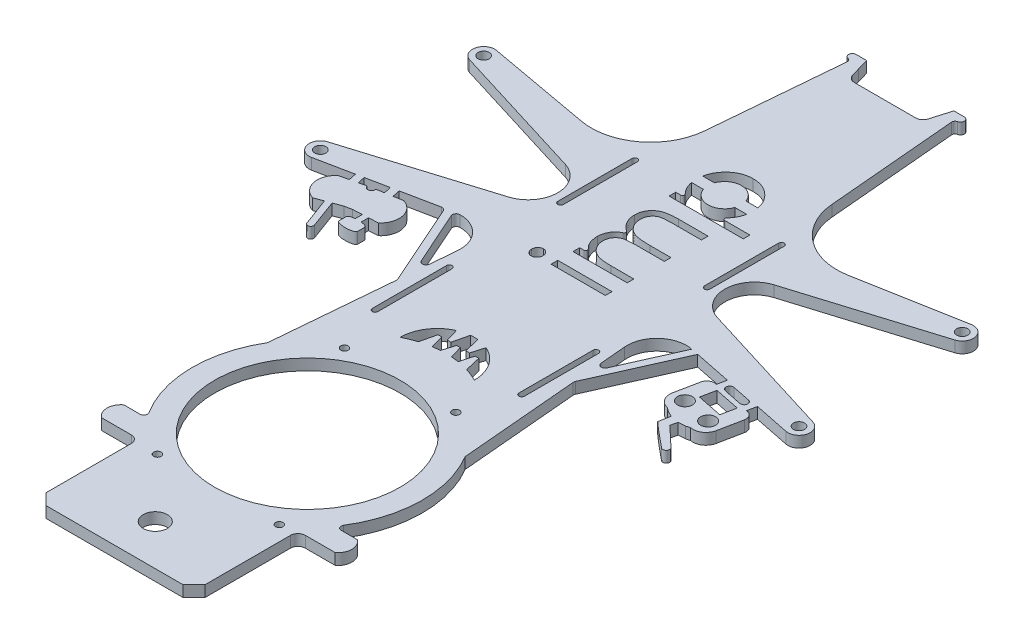
SolidWorks part; units mm, degrees
ref_plane "前视基准面" through (0, 0, 0) normal (0, 0, 1) x (1, 0, 0)
ref_plane "上视基准面" through (0, 0, 0) normal (0, 1, 0) x (1, 0, 0)
ref_plane "右视基准面" through (0, 0, 0) normal (1, 0, 0) x (0, 0, -1)
sketch "草图1" plane through (0, 0, 0) normal (0, 1, 0) x (1, 0, 0)
  line L5 (-65.3843, -19.1333) -> (-28.1418, -7.6445)
  line L6 (-63.9021, -24.9398) -> (-56.5526, -23.4451)
  line L8 (0, 0) -> (0, 91.5573) construction
  line L9 (0, 0) -> (-115.8836, 0) construction
  line L15 (0, 0) -> (0, -124.2991) construction
  line L16 (-15, -65) -> (15, -65) construction
  line L20 (-15.42, -115) -> (17.43, -115) construction
  line L21 (-28, -109.5) -> (-28, -90)
  line L22 (28, -109.5) -> (28, -90)
  line L23 (-17.5, -120) -> (17.5, -120)
  line L28 (22.5, -27) -> (22.5, 27) construction
  line L29 (-22.5, -27) -> (-22.5, 27) construction
  line L30 (28.1418, -7.6445) -> (65.3843, -19.1333)
  line L31 (28.1418, 7.6445) -> (65.3843, 19.1333)
  line L32 (-28, -90) -> (28, -90) construction
  line L33 (28, -90) -> (22.5, -27)
  line L34 (-28, -90) -> (-22.5, -27)
  line L36 (0, 0) -> (104.501, 0) construction
  line L37 (-28.1418, 7.6445) -> (-65.3843, 19.1333)
  line L39 (22.5, 70) -> (22.5, 27) construction
  line L40 (-22.5, 70) -> (-22.5, 27) construction
  line L41 (31.9307, 19.129) -> (63.9635, 24.9516) construction
  line L42 (-63.9635, 24.9516) -> (-31.9307, 19.129) construction
  line L43 (-17.1562, 34.2114) -> (-14.0779, 69.4717)
  line L44 (63.9635, 24.9516) -> (35.957, 19.8608)
  line L45 (-63.9635, 24.9516) -> (-35.957, 19.8608)
  line L46 (17.1562, 34.2114) -> (14.0779, 69.4717)
  line L51 (-49.203, -21.9504) -> (-47.2101, -31.7498) construction
  line L58 (-48.19, -31.9491) -> (-46.2301, -31.5505)
  line L59 (-41.8535, -20.4557) -> (-32.0641, -18.4647)
  line L65 (-14.4088, 65.6811) -> (14.4088, 65.6811) construction
  line L70 (-10.8845, 69.4717) -> (-10.1819, 67.1107)
  line L75 (10.8788, 69.4717) -> (10.1832, 67.115)
  line L76 (-8.265, 65.6811) -> (8.265, 65.6811)
  line L77 (-56.5526, -23.4451) -> (-41.8535, -20.4557) construction
  line L78 (-46.2301, -31.5505) -> (-43.7558, -31.4316)
  line L79 (-48.19, -31.9491) -> (-50.5246, -32.81)
  line L80 (-54.3603, -34.2244) -> (-39.6612, -31.235) construction
  line L81 (-48.7048, -24.4002) -> (-49.7844, -24.1095) construction
  line L82 (-48.7048, -24.4002) -> (-47.8245, -23.711) construction
  line L84 (41.8535, -20.4557) -> (32.0641, -18.4647)
  line L101 (-49.7844, -24.1095) -> (-47.8245, -23.711) construction
  line L103 (63.9021, -24.9398) -> (56.5526, -23.4451)
  line L106 (41.8535, -20.4557) -> (56.5526, -23.4451) construction
  line L107 (42.3935, -35.3623) -> (50.233, -36.9567) construction
  line L108 (39.6612, -31.235) -> (40.9566, -24.8654)
  line L109 (43.3151, -23.3041) -> (43.6091, -23.3639)
  line L110 (54.3603, -34.2244) -> (55.6557, -27.8548)
  line L111 (38.9637, -34.6648) -> (56.0543, -25.8949) construction
  line L112 (41.3552, -22.9055) -> (53.6628, -37.6542) construction
  line L113 (49.203, -21.9504) -> (41.4195, -60.2218) construction
  line L114 (43.6091, -23.3639) -> (44.8847, -23.1131) construction
  line L115 (44.8847, -23.1131) -> (52.7242, -24.7074) construction
  line L116 (52.7242, -24.7074) -> (53.8005, -25.4366) construction
  line L117 (53.8005, -25.4366) -> (54.0944, -25.4964)
  line L120 (44.938, -36.9003) -> (47.2899, -37.3786) construction
  line L121 (45.4995, -45.1782) -> (43.5396, -44.7797) construction
  line L122 (45.4995, -45.1782) -> (47.2899, -37.3786) construction
  line L123 (43.5396, -44.7797) -> (44.938, -36.9003) construction
  line L124 (43.2738, -36.0516) -> (49.1534, -37.2474) construction
  line L125 (47.2899, -37.3786) -> (49.1534, -37.2474)
  line L126 (44.938, -36.9003) -> (43.2738, -36.0516)
  line L127 (43.2738, -36.0516) -> (42.3935, -35.3623)
  line L128 (49.1534, -37.2474) -> (50.233, -36.9567)
  line L129 (43.1907, -31.4426) -> (51.0302, -33.0369) construction
  line L130 (40.7168, -24.8097) -> (55.8983, -27.8973) construction
  line L131 (52.7242, -24.7074) -> (53.1228, -22.7476) construction
  line L132 (44.8847, -23.1131) -> (45.2833, -21.1532) construction
  line L133 (53.1228, -22.7476) -> (56.5526, -23.4451) construction
  line L134 (41.8535, -20.4557) -> (45.2833, -21.1532) construction
  line L135 (45.6157, -39.5893) -> (53.5856, -46.6394) construction
  line L136 (44.3922, -39.9756) -> (46.3849, -41.7383)
  line L137 (46.8657, -39.2264) -> (47.8425, -40.0905)
  line L138 (47.8425, -40.0905) -> (46.3849, -41.7383) construction
  line L139 (47.2899, -37.3786) -> (46.8657, -39.2264)
  line L140 (44.938, -36.9003) -> (44.3922, -39.9756)
  line L141 (51.0114, -45.5639) -> (52.204, -44.2157) construction
  line L142 (47.8425, -40.0905) -> (52.204, -44.2157)
  line L143 (46.3849, -41.7383) -> (51.0114, -45.5639)
  line L144 (53.8005, -25.4366) -> (54.2987, -22.9867)
  line L145 (45.0757, -24.6826) -> (51.9353, -26.0777)
  line L146 (45.0757, -24.6826) -> (44.2785, -28.6024)
  line L147 (44.2785, -28.6024) -> (51.1381, -29.9975)
  line L148 (51.9353, -26.0777) -> (51.1381, -29.9975)
  line L149 (45.0757, -24.6826) -> (51.1381, -29.9975) construction
  line L150 (44.2785, -28.6024) -> (51.9353, -26.0777) construction
  line L151 (54.2987, -22.9867) -> (56.5526, -23.4451)
  line L152 (43.6091, -23.3639) -> (44.1073, -20.914)
  line L153 (41.8535, -20.4557) -> (44.1073, -20.914)
  line L154 (-47.8245, -23.711) -> (-45.8523, -23.3727)
  line L155 (-49.7844, -24.1095) -> (-51.732, -24.5684)
  line L156 (-56.1141, -25.601) -> (-48.1766, -23.9867) construction
  line L157 (-52.91, -29.4394) -> (-42.8653, -27.3966) construction
  line L158 (-42.9558, -31.3932) -> (-42.9558, -37.0074) construction
  line L159 (-51.2752, -33.0867) -> (-49.3498, -38.3078) construction
  line L160 (-49.3498, -38.3078) -> (-42.9558, -37.0074) construction
  line L161 (-41.8535, -20.4557) -> (-44.3033, -20.9539)
  line L162 (-44.3033, -20.9539) -> (-43.8802, -23.0344)
  line L163 (-45.8523, -23.3727) -> (-46.2632, -21.3525)
  line L164 (-56.5526, -23.4451) -> (-54.1027, -22.9469)
  line L165 (-54.1027, -22.9469) -> (-53.6796, -25.0273)
  line L166 (-51.732, -24.5684) -> (-52.1428, -22.5483)
  line L167 (-52.1428, -22.5483) -> (-46.2632, -21.3525)
  line L168 (-53.6796, -25.0273) -> (-56.1141, -25.601)
  line L169 (-43.8802, -23.0344) -> (-41.415, -22.6115)
  line L170 (-43.7558, -31.4316) -> (-43.7558, -33.3548)
  line L171 (-42.1558, -31.3548) -> (-42.1558, -33.3548)
  line L172 (-42.1558, -31.3548) -> (-39.6612, -31.235)
  line L173 (-45.4558, -34.0654) -> (-40.4558, -34.0654) construction
  line L174 (-42.9558, -34.8154) -> (-42.9558, -33.3154) construction
  line L175 (-45.4558, -36.0654) -> (-40.4558, -36.0654) construction
  line L176 (-42.9558, -36.8154) -> (-42.9558, -35.3154) construction
  line L177 (-40.4558, -36.0654) -> (-40.4558, -34.0654)
  line L178 (-45.4558, -36.0654) -> (-45.4558, -34.0654)
  line L179 (-50.5246, -32.81) -> (-47.7567, -40.3159)
  line L180 (-52.0257, -33.3635) -> (-49.2579, -40.8695)
  line L181 (-52.0257, -33.3635) -> (-54.3603, -34.2244)
  line L182 (11.7642, 72.4717) -> (14.5779, 72.4717)
  line L183 (-11.7642, 72.4717) -> (-14.5779, 72.4717)
  line L184 (11.7642, 72.4717) -> (10.8788, 69.4717)
  line L185 (-11.7642, 72.4717) -> (-10.8845, 69.4717)
  line L186 (46.5041, -22.6771) -> (51.4037, -23.6735) construction
  line L187 (46.7033, -21.6971) -> (51.603, -22.6936)
  line L188 (46.3048, -23.657) -> (51.2045, -24.6535)
  circle A0 centre (-64.5, 30) radius 1.5 construction
  circle A1 centre (64.5, 30) radius 1.5 construction
  circle A2 centre (64.5, -30) radius 1.5 construction
  circle A3 centre (-64.5, -30) radius 1.5 construction
  circle A4 centre (-64.5, 30) radius 3 construction
  circle A5 centre (64.5, 30) radius 3 construction
  circle A6 centre (64.5, -30) radius 3 construction
  circle A7 centre (-64.5, -30) radius 3 construction
  circle A10 centre (-64.5, 22) radius 1.5
  circle A11 centre (64.5, 22) radius 1.5
  circle A12 centre (64.5, -22) radius 1.5
  circle A13 centre (-64.5, -22) radius 1.5
  circle A22 centre (0, -90) radius 25
  circle A23 centre (-15, -65) radius 1
  circle A24 centre (15, -65) radius 1
  circle A25 centre (-15.42, -115) radius 1
  circle A26 centre (17.43, -115) radius 1
  arc A27 (-17.5, -120) -> (-28, -109.5) centre (-17.5, -109.5) cw
  arc A28 (17.5, -120) -> (28, -109.5) centre (17.5, -109.5) ccw
  arc A42 (63.9021, -24.9398) -> (65.3843, -19.1333) centre (64.5, -22) ccw
  arc A43 (65.3843, 19.1333) -> (63.9635, 24.9516) centre (64.5, 22) ccw
  arc A44 (28.1418, -7.6445) -> (28.1418, 7.6445) centre (30.5, 0) cw
  arc A47 (-65.3843, -19.1333) -> (-63.9021, -24.9398) centre (-64.5, -22) ccw
  arc A49 (-28.1418, -7.6445) -> (-28.1418, 7.6445) centre (-30.5, 0) ccw
  arc A50 (-22.5, -27) -> (-32.0641, -18.4647) centre (-30.4697, -26.3042) ccw
  arc A51 (-63.9635, 24.9516) -> (-65.3843, 19.1333) centre (-64.5, 22) ccw
  arc A52 (31.9307, 19.129) -> (22.5, 27) centre (30.5, 27) cw construction
  arc A53 (-31.9307, 19.129) -> (-22.5, 27) centre (-30.5, 27) ccw construction
  arc A54 (-35.957, 19.8608) -> (-17.1562, 34.2114) centre (-33.0955, 35.6029) ccw
  arc A55 (17.1562, 34.2114) -> (35.957, 19.8608) centre (33.0955, 35.6029) ccw
  arc A56 (-8.265, 65.6811) -> (-10.1819, 67.1107) centre (-8.265, 67.6811) cw
  arc A57 (10.1832, 67.115) -> (8.265, 65.6811) centre (8.265, 67.6811) cw
  arc A79 (22.5, -27) -> (32.0641, -18.4647) centre (30.4697, -26.3042) cw
  arc A80 (55.6557, -27.8548) -> (54.0944, -25.4964) centre (53.6959, -27.4562) ccw
  arc A81 (40.9566, -24.8654) -> (43.3151, -23.3041) centre (42.9165, -25.264) cw
  arc A83 (43.5396, -44.7797) -> (45.4995, -45.1782) centre (44.5196, -44.9789) ccw construction
  arc A84 (54.3603, -34.2244) -> (50.233, -36.9567) centre (50.9305, -33.5269) cw
  arc A85 (39.6612, -31.235) -> (42.3935, -35.3623) centre (43.091, -31.9325) ccw
  circle A86 centre (43.1907, -31.4426) radius 2
  circle A87 centre (51.0302, -33.0369) radius 2
  arc A88 (44.8847, -23.1131) -> (41.8535, -20.4557) centre (40.7168, -24.8097) ccw construction
  arc A89 (52.7242, -24.7074) -> (56.5526, -23.4451) centre (55.8983, -27.8973) cw construction
  arc A90 (51.0114, -45.5639) -> (52.204, -44.2157) centre (51.6077, -44.8898) ccw
  arc A91 (-39.6612, -31.235) -> (-41.415, -22.6115) centre (-42.8653, -27.3966) ccw
  arc A92 (-54.3603, -34.2244) -> (-56.1141, -25.601) centre (-52.91, -29.4394) cw
  arc A93 (-49.2579, -40.8695) -> (-47.7567, -40.3159) centre (-48.5073, -40.5927) ccw
  arc A94 (14.5779, 72.4717) -> (14.7779, 70.4717) centre (14.5779, 71.4617) cw
  arc A95 (14.0779, 69.4717) -> (14.7779, 70.4717) centre (14.9532, 69.604) cw
  arc A96 (-14.0779, 69.4717) -> (-14.7779, 70.4717) centre (-14.9532, 69.604) ccw
  arc A97 (-14.5779, 72.4717) -> (-14.7779, 70.4717) centre (-14.5779, 71.4617) ccw
  arc A98 (-49.7844, -24.1095) -> (-47.8245, -23.711) centre (-48.8044, -23.9103) ccw
  arc A99 (46.7033, -21.6971) -> (46.3048, -23.657) centre (46.5041, -22.6771) ccw
  arc A100 (51.2045, -24.6535) -> (51.603, -22.6936) centre (51.4037, -23.6735) ccw
  ellipse E0 centre (-42.9558, -36.0654) end of major axis (-40.4558, -36.0654) minor radius 0.75 (-45.4558, -36.0654) -> (-40.4558, -36.0654) ccw
  ellipse E1 centre (-42.9558, -34.0654) end of major axis (-45.4558, -34.0654) minor radius 0.75 (-40.4558, -34.0654) -> (-42.1558, -33.3548) ccw
  ellipse E2 centre (-42.9558, -34.0654) end of major axis (-45.4558, -34.0654) minor radius 0.75 (-43.7558, -33.3548) -> (-45.4558, -34.0654) ccw
  point P0 (0, 0)
  point P55 (47.509, -30.2799)
  point P109 (-9.7565, 65.6811)
  point P112 (9.76, 65.6811)
  point P182 (48.1069, -27.34)
  point P213 (48.9539, -23.1753)
  point P227 (0, 0)
  dimension "D1" = 3
  dimension "D6" = 6
  dimension "D7" = 6
  dimension "D8" = 6
  dimension "D9" = 6
  dimension "D15" = 3
  dimension "D18" = 6
  dimension "D19" = 16
  dimension "D20" = 8
  dimension "D21" = 22
  dimension "D22" = 50
  dimension "D28" = 2
  dimension "D31" = 2
  dimension "D25" = 45
  dimension "D37" = 27
  dimension "D38" = 16
  dimension "D39" = 15
  dimension "D40" = 12
  dimension "D41" = 6
  dimension "D44" = 8
  dimension "D45" = 5.2
  dimension "D27" = 22.5
  dimension "D47" = 10.5
  dimension "D48" = 15
  dimension "D17" = 8
  dimension "D12" = 6
  dimension "D13" = 8
  dimension "D16" = 8
  dimension "D60" = 2
  dimension "D61" = 2
  dimension "D62" = 1
  dimension "D67" = 7.5
  dimension "D70" = 0.2
  dimension "D74" = 6
  dimension "D77" = 0.8
  dimension "D81" = 2.4
  dimension "D66" = 2
  dimension "D86" = 1
  dimension "D90" = 3
  dimension "D93" = 2
  dimension "D79" = 2.4743
  dimension "D82" = 1
  dimension "D87" = 1
  dimension "D91" = 3.5
  dimension "D92" = 3.5
  dimension "D102" = 4
  dimension "D103" = 4.5
  dimension "D114" = 0.9
  dimension "D68" = 5
  dimension "D69" = 5
  dimension "D78" = 5
  dimension "D130" = 0.5
  dimension "D96" = 1
  dimension "D2" = 129
  dimension "D3" = 60
  dimension "D4" = 30
  dimension "D5" = 64.5
  dimension "D11" = 27
  dimension "D14" = 9.7565
  dimension "D23" = 30
  dimension "D24" = 15
  dimension "D26" = 30
  dimension "D29" = 32.85
  dimension "D30" = 2.43
  dimension "D32" = 27
  dimension "D33" = 28
  dimension "D34" = 28
  dimension "D35" = 35
  dimension "D36" = 17.5
  dimension "D42" = 45
  dimension "D43" = 5.2
  dimension "D46" = 120
  dimension "D49" = 2.4933
  dimension "D50" = 2
  dimension "D51" = 1
  dimension "D52" = 15
  dimension "D53" = 7.5
  dimension "D54" = 0.5
  dimension "D55" = 4
  dimension "D56" = 4
  dimension "D57" = 65.6811
  dimension "D58" = 10.1819
  dimension "D59" = 10.1832
  dimension "D63" = 2
  dimension "D64" = 0.8
  dimension "D65" = 15
  dimension "D71" = 8
  dimension "D72" = 2
  dimension "D73" = 2.5
  dimension "D75" = 5
  dimension "D76" = 2
  dimension "D80" = 2
  dimension "D83" = 8
  dimension "D84" = 1.2
  dimension "D85" = 1
  dimension "D88" = 0.5
  dimension "D89" = 3
  dimension "D94" = 4
  dimension "D95" = 4
  dimension "D97" = 8.265
  dimension "D98" = 3.7906
  dimension "D99" = 8.265
  dimension "D100" = 9.76
  dimension "D101" = 22.5
  dimension "D104" = 60
  dimension "D105" = 10.8845
  dimension "D106" = 10.8788
  dimension "D107" = 2.5
  dimension "D108" = 1.1
  dimension "D109" = 1.1
  dimension "D110" = 2
  dimension "D111" = 0.9
  dimension "D112" = 0.9
  dimension "D113" = 6
  dimension "D115" = 4
  dimension "D116" = 7
  dimension "D117" = 1.5
  dimension "D118" = 5
  dimension "D119" = 1.5
  dimension "D120" = 1.5
  dimension "D121" = 2
  dimension "D122" = 2
  dimension "D123" = 1.6
  dimension "D124" = 0.8
  dimension "D125" = 8
  dimension "D126" = 2.4882
  dimension "D127" = 3
  dimension "D128" = 0.2
  dimension "D129" = 1
  dimension "D131" = 1.25
  dimension "D132" = 2
  dimension "D133" = 5
extrude "凸台-拉伸1" add sketch "草图1" along normal blind 3
sketch "草图2" plane through (0, 0, 0) normal (0, -1, 0) x (1, 0, 0)
  line L0 (0, 133.3282) -> (0, -97.043) construction
  line L1 (-19.75, 2) -> (-19.75, -18) construction
  line L2 (-19, 2) -> (-19, -18)
  line L3 (-20.5, 2) -> (-20.5, -18)
  line L4 (19.75, 2) -> (19.75, -18) construction
  line L5 (20.5, 2) -> (20.5, -18)
  line L6 (19, 2) -> (19, -18)
  line L7 (0, 0) -> (56.7659, 0) construction
  line L8 (-19.75, 52) -> (-19.75, 32) construction
  line L9 (-19, 52) -> (-19, 32)
  line L10 (-20.5, 52) -> (-20.5, 32)
  line L11 (19.75, 52) -> (19.75, 32) construction
  line L12 (20.5, 52) -> (20.5, 32)
  line L13 (19, 52) -> (19, 32)
  arc A0 (-19, 2) -> (-20.5, 2) centre (-19.75, 2) ccw
  arc A1 (-20.5, -18) -> (-19, -18) centre (-19.75, -18) ccw
  arc A2 (20.5, 2) -> (19, 2) centre (19.75, 2) ccw
  arc A3 (19, -18) -> (20.5, -18) centre (19.75, -18) ccw
  arc A4 (-19, 52) -> (-20.5, 52) centre (-19.75, 52) ccw
  arc A5 (-20.5, 32) -> (-19, 32) centre (-19.75, 32) ccw
  arc A6 (20.5, 52) -> (19, 52) centre (19.75, 52) ccw
  arc A7 (19, 32) -> (20.5, 32) centre (19.75, 32) ccw
  arc A8 (-10, 55) -> (10, 55) centre (0, 55) ccw
  arc A9 (-10, 55) -> (10, 55) centre (0, 74.5959) ccw
  point P5 (-19.75, -8)
  point P10 (19.75, -8)
  point P19 (-19.75, 42)
  point P26 (19.75, 42)
  dimension "D6" = 42
  dimension "D8" = 10
  dimension "D9" = 22
  dimension "D1" = 1.5
  dimension "D2" = 20
  dimension "D3" = 19
  dimension "D4" = 19
  dimension "D5" = 8
  dimension "D7" = 55
  dimension "D10" = 10
extrude "切除-拉伸1" cut sketch "草图2" against normal blind 3
sketch "草图3" plane through (0, 0, 0) normal (0, -1, 0) x (1, 0, 0)
  line L0 (0, 67.5428) -> (0, 45) construction
  line L1 (-5, 60.2388) -> (-5, 45) construction
  line L2 (5, 60.0167) -> (5, 45) construction
  line L3 (-1.5, 52.6471) -> (-0.5, 49.2959)
  line L4 (0.5, 49.2959) -> (1.5, 52.6471)
  line L5 (-5, 48.7959) -> (5, 48.7959) construction
  line L6 (-4.5, 49.2959) -> (-3.5, 52.8761)
  line L7 (-6.5, 53.5781) -> (-5.5, 49.2959)
  line L8 (4.5, 49.2959) -> (3.5, 52.8761)
  line L9 (5.5, 49.2959) -> (6.5, 53.5781)
  line L10 (-5, 52.5959) -> (5, 52.5959) construction
  line L11 (-5, 45) -> (5, 45) construction
  line L12 (-2.5, 52.5959) -> (-2.5, 44.2103) construction
  line L13 (2.5, 52.5959) -> (2.5, 43.8348) construction
  line L14 (-2, 49.2959) -> (-1, 45.0501)
  line L15 (-3, 49.2959) -> (-4, 45.8348)
  line L16 (2, 49.2959) -> (1, 45.0501)
  line L17 (3, 49.2959) -> (4, 45.8348)
  line L18 (-6.5, 53.5781) -> (-6.5, 54.5781)
  line L19 (-6.5, 54.5781) -> (6.5, 54.5781)
  line L20 (6.5, 54.5781) -> (6.5, 53.5781)
  line L21 (-3.5, 52.8761) -> (-3.5, 53.8761)
  line L22 (-3.5, 53.8761) -> (-1.5, 53.8761)
  line L23 (-1.5, 53.8761) -> (-1.5, 52.6471)
  line L24 (1.5, 52.6471) -> (1.5, 53.8761)
  line L25 (1.5, 53.8761) -> (3.5, 53.8761)
  line L26 (3.5, 53.8761) -> (3.5, 52.8761)
  line L27 (-4, 45.8348) -> (-4, 43.8348)
  line L28 (-4, 43.8348) -> (4, 43.8348)
  line L29 (4, 43.8348) -> (4, 45.8348)
  line L30 (-1, 45.0501) -> (-1, 44.0501)
  line L31 (-1, 44.0501) -> (1, 44.0501)
  line L32 (1, 44.0501) -> (1, 45.0501)
  line L33 (-5.5, 49.2959) -> (-4.5, 49.2959)
  line L34 (-0.5, 49.2959) -> (0.5, 49.2959)
  line L35 (4.5, 49.2959) -> (5.5, 49.2959)
  line L36 (-3, 49.2959) -> (-2, 49.2959)
  line L37 (2, 49.2959) -> (3, 49.2959)
  arc A0 (-10, 55) -> (10, 55) centre (0, 74.5959) ccw construction
  arc A1 (-10, 55) -> (10, 55) centre (0, 74.5959) ccw construction
  arc A2 (-10, 55) -> (10, 55) centre (0, 55) ccw construction
  arc A3 (-10, 55) -> (10, 55) centre (0, 55) ccw construction
  point P14 (0, 0)
  point P28 (0, 0)
  point P32 (0, 0)
  point P35 (0, 0)
  point P51 (0, 0)
  point P52 (0, 0)
  point P53 (0, 0)
  point P54 (0, 0)
  point P56 (0, 0)
  point P60 (0, 0)
  point P61 (0, 0)
  point P62 (0, 0)
  dimension "D21" = 0.5
  dimension "D25" = 0.5
  dimension "D26" = 1
  dimension "D28" = 1
  dimension "D33" = 0.5
  dimension "D1" = 5
  dimension "D2" = 5
  dimension "D3" = 7.5959
  dimension "D4" = 3
  dimension "D5" = 1.5
  dimension "D6" = 1.5
  dimension "D7" = 1.5
  dimension "D8" = 3
  dimension "D9" = 1.5
  dimension "D10" = 3.8
  dimension "D11" = 2.5
  dimension "D12" = 5
  dimension "D13" = 1.5
  dimension "D14" = 1.5
  dimension "D15" = 1.5
  dimension "D16" = 1.5
  dimension "D17" = 1
  dimension "D18" = 1
  dimension "D19" = 1
  dimension "D20" = 2
  dimension "D22" = 0.5
  dimension "D23" = 0.5
  dimension "D24" = 1
  dimension "D27" = 0.5
  dimension "D29" = 0.5
  dimension "D30" = 1
  dimension "D31" = 0.5
  dimension "D32" = 1
extrude "凸台-拉伸2" add sketch "草图3" against normal blind 3
sketch "草图4" plane through (0, 0, 0) normal (0, -1, 0) x (1, 0, 0)
  line L0 (0, 0) -> (0, 140.5969) construction
  line L1 (-28, 108) -> (-21.4476, 108)
  line L2 (-17.5, 120) -> (17.5, 120) construction
  line L3 (-28, 90) -> (28, 90) construction
  line L4 (-28, 90) -> (-28, 109.5) construction
  line L5 (28, 109.5) -> (28, 90) construction
  line L6 (-21.4476, 114) -> (-21.4476, 119.2297)
  line L7 (21.4476, 119.2297) -> (21.4476, 114)
  line L8 (21.4476, 108) -> (28, 108)
  line L9 (-21.4476, 114) -> (-26.9868, 114)
  line L10 (21.4476, 114) -> (26.9868, 114)
  line L11 (-28, 108) -> (-28, 90)
  line L12 (28, 108) -> (28, 90)
  circle A0 centre (0, 90) radius 25 construction
  circle A1 centre (0, 90) radius 25 construction
  arc A2 (-21.4476, 108) -> (-28, 90) centre (0, 90) ccw
  arc A3 (28, 90) -> (21.4476, 108) centre (0, 90) ccw
  arc A4 (-17.5, 120) -> (-28, 109.5) centre (-17.5, 109.5) ccw construction
  arc A5 (28, 109.5) -> (17.5, 120) centre (17.5, 109.5) ccw construction
  arc A6 (-21.4476, 119.2297) -> (-26.9868, 114) centre (-17.5, 109.5) ccw
  arc A7 (26.9868, 114) -> (21.4476, 119.2297) centre (17.5, 109.5) ccw
  dimension "D1" = 12
  dimension "D4" = 6
  dimension "D5" = 6
extrude "切除-拉伸2" cut sketch "草图4" against normal blind 3
sketch "草图6" plane through (0, 0, 0) normal (0, -1, 0) x (1, 0, 0)
  line L0 (-21.4476, 119.2297) -> (-21.4476, 139)
  line L1 (-18.4476, 142) -> (18.4476, 142)
  line L2 (21.4476, 139) -> (21.4476, 119.2297)
  line L3 (-17.5, 120) -> (17.5, 120) construction
  line L4 (0, 0) -> (0, 166.5632) construction
  line L5 (-21.4476, 131) -> (21.4476, 131) construction
  line L6 (-21.4476, 139) -> (-18.4476, 142)
  line L7 (18.4476, 142) -> (21.4476, 139)
  line L8 (-21.4476, 119.2297) -> (21.4476, 119.2297)
  circle A0 centre (0, 131) radius 3.25
  point P1 (-21.4476, 142)
  point P4 (21.4476, 142)
  dimension "D3" = 6.5
  dimension "D1" = 22
  dimension "D2" = 11
extrude "凸台-拉伸3" add sketch "草图6" against normal blind 3
sketch "草图7" plane through (0, 0, 0) normal (0, -1, 0) x (1, 0, 0)
  line L0 (-21.4476, 108) -> (-28, 108) construction
  line L1 (-21.4476, 108) -> (-28, 108) construction
  line L2 (28, 108) -> (21.4476, 108) construction
  line L3 (28, 108) -> (21.4476, 108) construction
  line L4 (-22.5, 27) -> (-28, 90) construction
  line L5 (-26.6119, 74.1001) -> (-28, 90)
  line L6 (28, 90) -> (22.5, 27) construction
  line L7 (28, 90) -> (26.6119, 74.1001)
  line L8 (-25.2389, 108) -> (-21.4476, 108)
  line L9 (21.4476, 108) -> (25.2389, 108)
  circle A0 centre (0, 90) radius 25 construction
  circle A1 centre (0, 90) radius 25 construction
  arc A2 (-25.2389, 108) -> (-26.6119, 74.1001) centre (0, 90) ccw
  arc A3 (26.6119, 74.1001) -> (25.2389, 108) centre (0, 90) ccw
  arc A4 (-21.4476, 108) -> (-28, 90) centre (0, 90) ccw construction
  arc A5 (-21.4476, 108) -> (-28, 90) centre (0, 90) ccw
  arc A6 (28, 90) -> (21.4476, 108) centre (0, 90) ccw construction
  arc A7 (28, 90) -> (21.4476, 108) centre (0, 90) ccw
  dimension "D1" = 62
extrude "凸台-拉伸4" add sketch "草图7" against normal blind 3
sketch "草图8" plane through (0, 3, 0) normal (0, 1, 0) x (1, 0, 0)
  line L0 (7.8825, -19.3796) -> (7.8825, 18.6946) construction
  text T0 "imp" font "Century Gothic" height 20
  point P2 (0, -41.9231)
  point P4 (7.0339, -42.9874)
  point P6 (9.498, -41.0379)
  point P7 (4.698, -40.4737)
  point P8 (3.934, -33.8523)
  point P9 (3.5944, 18.6946)
  point P10 (5.0376, -17.893)
  point P11 (4.9682, -21.9784)
  point P12 (7.5584, -21.6843)
  point P13 (0, 0)
  point P14 (6.1992, -19.0791)
  point P15 (8.3513, -18.7959)
  point P16 (7.0487, -18.2296)
  point P17 (8.778, -18.8516)
  point P18 (0, 0)
  point P19 (0, 0)
  point P20 (0, 0)
  point P21 (0, 0)
  point P22 (7.8825, -19.3796)
  dimension "D1" = 7.8825
  dimension "D2" = 19.3796
extrude "切除-拉伸3" cut sketch "草图8" against normal blind 10 body kept at (44.938, 0, 36.9003)
sketch "草图10" plane through (0, 0, 0) normal (0, -1, 0) x (1, 0, 0)
  line L0 (-26.9868, 114) -> (-31.4868, 114)
  line L2 (-31.4868, 108) -> (-26.9868, 108)
  line L3 (-26.9868, 108) -> (-26.9868, 114)
  line L4 (-25.2389, 108) -> (-28, 108) construction
  line L5 (0, 0) -> (0, 153.1529) construction
  line L10 (26.9868, 108) -> (26.9868, 114)
  line L11 (31.4868, 108) -> (26.9868, 108)
  line L12 (26.9868, 114) -> (31.4868, 114)
  arc A0 (-31.4868, 114) -> (-31.4868, 108) centre (-29.2368, 111) ccw
  arc A1 (31.4868, 114) -> (31.4868, 108) centre (29.2368, 111) cw
  dimension "D1" = 3.75
  dimension "D2" = 4.5
  dimension "D3" = 4.5
extrude "凸台-拉伸6" add sketch "草图10" against normal blind 3
fillet "圆角2" radius 2 1 edges at (-21.4476, 1.5, 114)
fillet "圆角3" radius 2 1 edges at (21.4476, 1.5, 114)
fillet "圆角4" radius 1 1 edges at (-25.2389, 1.5, 108)
fillet "圆角5" radius 1 1 edges at (25.2389, 1.5, 108)
sketch "草图11" plane through (0, 0, 0) normal (0, -1, 0) x (1, 0, 0)
  line L0 (-22.5, 27) -> (-26.6119, 74.1001) construction
  line L1 (-22.5, 27) -> (-26.6119, 74.1001) construction
  line L2 (-44.3033, 20.9539) -> (-32.0641, 18.4647) construction
  line L3 (-44.3033, 20.9539) -> (-32.0641, 18.4647) construction
  line L4 (-32.0641, 18.4647) -> (-23.4449, 37.8236)
  line L5 (-32.0641, 18.4647) -> (30.3166, 18.4647) construction
  line L6 (-23.8038, 41.9347) -> (-34.0716, 18.873)
  line L7 (-23.8038, 41.9347) -> (-23.4449, 37.8236)
  line L8 (-34.0716, 18.873) -> (-32.0641, 18.4647)
  line L9 (0, 0) -> (0, 75.6123) construction
  line L10 (34.0716, 18.873) -> (32.0641, 18.4647)
  line L11 (23.8038, 41.9347) -> (23.4449, 37.8236)
  line L12 (23.8038, 41.9347) -> (34.0716, 18.873)
  line L13 (32.0641, 18.4647) -> (23.4449, 37.8236)
  dimension "D1" = 66
  dimension "D2" = 2
extrude "凸台-拉伸7" add sketch "草图11" against normal blind 3
fillet "圆角6" radius 1 1 edges at (23.8038, 1.5, 41.9347)
fillet "圆角7" radius 1 1 edges at (23.4449, 1.5, 37.8236)
fillet "圆角11" radius 1 1 edges at (-23.8038, 1.5, 41.9347)
fillet "圆角12" radius 1 1 edges at (-34.0716, 1.5, 18.873)
fillet "圆角13" radius 1 1 edges at (-23.4449, 1.5, 37.8236)
fillet "圆角14" radius 1 1 edges at (-32.0641, 1.5, 18.4647)
fillet "圆角22" radius 0.5 1 edges at (-4.1928, 1.5, 9.8924)
fillet "圆角23" radius 0.5 1 edges at (-3.4596, 1.5, 0.2009)
fillet "圆角24" radius 0.5 1 edges at (-4.0286, 1.5, -16.0051)
fillet "圆角25" radius 0.5 1 edges at (5.2343, 1.5, -16.0051)
ref_plane "基准面1" through (-5.1944, 0, -4.8472) normal (-0.0288, 0, 0.9996) x (0.9996, 0, 0.0288)
sketch "草图13" plane through (0, 0, 0) normal (0, -1, 0) x (1, 0, 0)
  line L0 (-6.9893, -21.9105) -> (8.1374, -21.9105) construction
  line L1 (0.5607, -29.5941) -> (0.5607, -14.2102) construction
  line L2 (4.8034, -20.4105) -> (9.8034, -20.4105)
  line L3 (9.8034, -20.4105) -> (9.8034, -23.4105)
  line L4 (9.8034, -23.4105) -> (4.8034, -23.4105)
  line L5 (13.2671, -14.2102) -> (-6.7329, -14.2102) construction
  line L6 (-8.6819, -20.4105) -> (-8.6819, -23.4105)
  line L7 (-8.6819, -23.4105) -> (-3.6819, -23.4105)
  line L8 (-3.6819, -20.4105) -> (-8.6819, -20.4105)
  arc A0 (4.8034, -20.4105) -> (-3.6819, -20.4105) centre (0.5607, -21.9105) ccw
  arc A1 (-3.6819, -23.4105) -> (4.8034, -23.4105) centre (0.5607, -21.9105) ccw
  spline S1 degree 3 poles (-5.0243, -16.8582) (-5.1415, -16.9756) (-5.4461, -17.3038) (-5.8828, -17.8811) (-6.2972, -18.6036) (-6.6033, -19.3734) (-6.8311, -20.1796) (-6.9649, -21.0313) (-6.9811, -21.6136) (-6.9893, -21.9105) knots 0.190736 0.190736 0.190736 0.190736 0.26303 0.385707 0.505717 0.625137 0.74612 0.870524 1 1 1 1 construction
  spline S3 degree 3 poles (8.1389, -21.9666) (8.1309, -21.6763) (8.1152, -21.103) (7.9754, -20.2624) (7.7458, -19.4571) (7.4239, -18.6894) (7.0104, -17.9571) (6.5671, -17.3461) (6.2548, -16.9858) (6.1245, -16.846) knots 0 0 0 0 0.126833 0.250437 0.371271 0.492148 0.613426 0.738014 0.821523 0.821523 0.821523 0.821523 construction
  spline S4 degree 3 poles (0.5347, -29.5948) (0.7942, -29.5878) (1.3058, -29.574) (2.0572, -29.4669) (2.78, -29.2957) (3.473, -29.0496) (4.1358, -28.7317) (4.7678, -28.3448) (5.3689, -27.8883) (5.9309, -27.3666) (6.4486, -26.8006) (6.9014, -26.1956) (7.2817, -25.5609) (7.5993, -24.9) (7.8387, -24.207) (8.0113, -23.4852) (8.1178, -22.735) (8.1318, -22.2247) (8.1389, -21.9666) knots 0 0 0 0 0.064921 0.128034 0.189574 0.25058 0.311733 0.37325 0.435763 0.500346 0.564949 0.627528 0.689157 0.749865 0.81076 0.8723 0.935413 1 1 1 1 construction
  point P8 (0, 0)
  point P11 (0, 0)
  point P16 (0, 0)
  point P19 (0, 0)
  point P22 (0, 0)
  point P23 (0, 0)
  point P24 (0, 0)
  point P25 (0.574, -20.025)
  point P26 (0, 0)
  point P27 (0, 0)
  point P28 (0, 0)
  dimension "D1" = 9
  dimension "D2" = 3
  dimension "D3" = 7.7003
  dimension "D4" = 15.1267
  dimension "D5" = 7.55
  dimension "D6" = 1.5
  dimension "D7" = 5
extrude "凸台-拉伸8" add sketch "草图13" against normal blind 3
